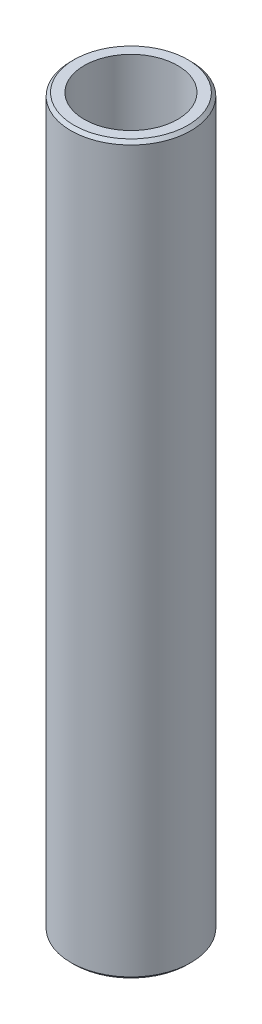
SolidWorks part; units mm, degrees
ref_plane "Front Plane" through (0, 0, 0) normal (0, 0, 1) x (1, 0, 0)
ref_plane "Top Plane" through (0, 0, 0) normal (0, 1, 0) x (1, 0, 0)
ref_plane "Right Plane" through (0, 0, 0) normal (1, 0, 0) x (0, 0, -1)
sketch "Sketch1" plane through (0, 0, 0) normal (0, 1, 0) x (1, 0, 0)
  circle A0 centre (0, 0) radius 47.5
  dimension "SHAFT_OD" = 95
extrude "Boss-Extrude1" add sketch "Sketch1" along normal blind 575.0806
sketch "Sketch2" plane through (0, 0, 0) normal (0, 1, 0) x (1, 0, 0)
  circle A0 centre (0, 0) radius 36.9738
  dimension "BORE_D" = 73.9476
extrude "Cut-Extrude1" cut sketch "Sketch2" along normal through all
chamfer "Chamfer1" distance 2.47 angle 45 2 edges at (0, 575.0806, 47.5) (0, 0, 47.5)
